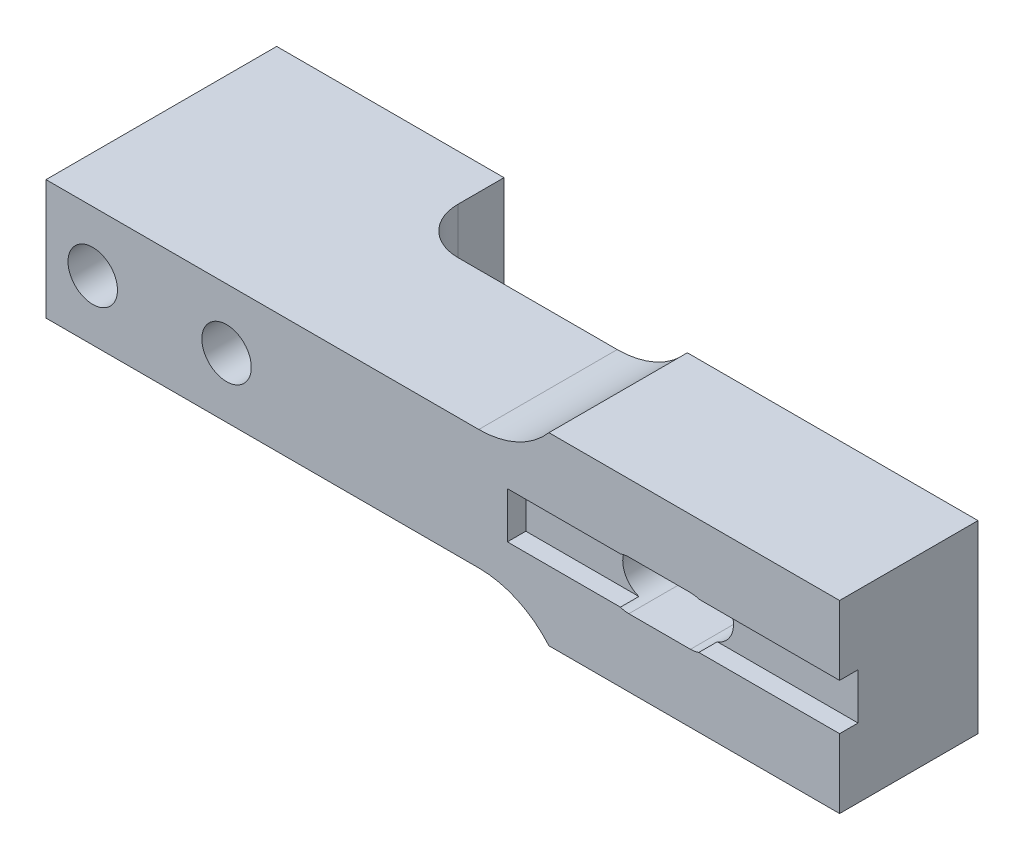
SolidWorks part; units mm, degrees
ref_plane "Front Plane" through (0, 0, 0) normal (0, 0, 1) x (1, 0, 0)
ref_plane "Top Plane" through (0, 0, 0) normal (0, 1, 0) x (1, 0, 0)
ref_plane "Right Plane" through (0, 0, 0) normal (1, 0, 0) x (0, 0, -1)
sketch "Sketch1" plane through (0, 0, 0) normal (0, 0, 1) x (1, 0, 0)
  line L0 (0, 0) -> (80, 0) construction
  line L1 (0, 13) -> (24.634, 13)
  line L2 (0, 13) -> (0, 0)
  line L3 (0, 0) -> (24.634, 0)
  line L4 (24.634, 13) -> (24.634, 0)
  line L5 (5.067, 6.5) -> (0, 6.5) construction
  line L6 (24.634, 6.5) -> (19.567, 6.5) construction
extrude "Boss-Extrude1" add sketch "Sketch1" along normal blind 10
sketch "Sketch4" plane through (0, 0, 10) normal (0, 0, 1) x (1, 0, 0)
  line L0 (24.634, 13) -> (0, 13) construction
  line L1 (0, 0) -> (82.5, 0)
  line L2 (0, 0) -> (0, 13)
  line L3 (0, 13) -> (82.5, 13)
  line L4 (82.5, 0) -> (82.5, 13)
  line L5 (80, 0) -> (80, 13) construction
  dimension "D1" = 2.5
extrude "Boss-Extrude4" add sketch "Sketch4" along normal blind 15
sketch "Sketch5" plane through (0, 0, 25) normal (0, 0, 1) x (1, 0, 0)
  line L0 (82.5, 0) -> (82.5, 13) construction
  line L1 (54.5, -3.5) -> (82.5, -3.5)
  line L2 (54.5, -3.5) -> (54.5, 0)
  line L3 (54.5, 16.5) -> (82.5, 16.5)
  line L4 (82.5, -3.5) -> (82.5, 0)
  line L5 (54.5, -3.5) -> (82.5, 16.5) construction
  line L6 (68.5, 0) -> (68.5, 13) construction
  line L7 (0, 0) -> (82.5, 0) construction
  line L8 (82.5, 13) -> (0, 13) construction
  line L9 (54.5, 0) -> (82.5, 0)
  line L10 (82.5, 13) -> (54.5, 13)
  line L11 (54.5, 13) -> (54.5, 16.5)
  line L12 (82.5, 13) -> (82.5, 16.5)
  point P13 (68.5, 6.5)
  point P14 (68.5, 6.5)
  dimension "D1" = 20
  dimension "D2" = 28
extrude "Boss-Extrude5" add sketch "Sketch5" against normal up to surface (15 mm away) up to face at (53.567, 6.5, 10)
sketch "Sketch6" plane through (0, 0, 25) normal (0, 0, 1) x (1, 0, 0)
  line L0 (54.5, 0) -> (54.5, 13) construction
  line L1 (63.16, 6.5) -> (69.84, 6.5) construction
  line L2 (63.16, 9.16) -> (69.84, 9.16)
  line L3 (63.16, 3.84) -> (69.84, 3.84)
  arc A0 (63.16, 9.16) -> (63.16, 3.84) centre (63.16, 6.5) ccw
  arc A1 (69.84, 3.84) -> (69.84, 9.16) centre (69.84, 6.5) ccw
  point P6 (66.5, 6.5)
  point P15 (54.5, 6.5)
  point P16 (60.5, 6.5)
  point P17 (72.5, 6.5)
  dimension "D1" = 5.32
  dimension "D2" = 6
  dimension "D3" = 12
extrude "Cut-Extrude1" cut sketch "Sketch6" against normal through all
sketch "Sketch7" plane through (0, 0, 25) normal (0, 0, 1) x (1, 0, 0)
  line L0 (50, 13) -> (50, 0) construction
  line L1 (50, 6.5) -> (82.5, 6.5) construction
  line L2 (82.5, -3.5) -> (82.5, 16.5) construction
  line L3 (66.25, 6.5) -> (66.25, 9) construction
  line L4 (50, 9) -> (82.5, 9)
  line L5 (50, 9) -> (50, 4)
  line L6 (50, 4) -> (82.5, 4)
  line L7 (82.5, 9) -> (82.5, 4)
  line L8 (66.25, 6.5) -> (66.25, 4) construction
  line L9 (0, 0) -> (54.5, 0) construction
  line L10 (54.5, 13) -> (0, 13) construction
  line L11 (54.5, 16.5) -> (54.5, 13) construction
  dimension "D1" = 5
  dimension "D2" = 4.5
extrude "Cut-Extrude2" cut sketch "Sketch7" against normal blind 2
sketch "Sketch11" plane through (0, 0, 0) normal (0, 0, -1) x (-1, 0, 0)
  line L0 (0, 6.5) -> (-24.634, 6.5) construction
  line L1 (0, 13) -> (0, 0) construction
  line L2 (-24.634, 0) -> (-24.634, 13) construction
  circle A0 centre (-5.067, 6.5) radius 2.68
  circle A1 centre (-19.567, 6.5) radius 2.68
  dimension "D3" = 5.36
  dimension "D4" = 5.36
  dimension "D1" = 5.067
  dimension "D2" = 14.5
extrude "Cut-Extrude3" cut sketch "Sketch11" against normal through all
fillet "Fillet1" radius 10 2 edges at (54.5, 13, 17.5) (54.5, 0, 17.5)
fillet "Fillet2" radius 5 1 edges at (24.634, 6.5, 10)
sketch "Sketch12" plane through (82.5, 0, 0) normal (1, 0, 0) x (0, 0, -1)
  line L8 (-25, 16.5) -> (-25, 9)
  line L9 (-25, 9) -> (-23, 9)
  line L10 (-23, 9) -> (-23, 4)
  line L11 (-23, 4) -> (-25, 4)
  line L12 (-25, 4) -> (-25, -3.5)
  line L13 (-25, -3.5) -> (-10, -3.5)
  line L14 (-10, -3.5) -> (-10, 16.5)
  line L15 (-10, 16.5) -> (-25, 16.5)
  line L16 (-25, 16.5) -> (-25, 9)
  line L17 (-25, 9) -> (-23, 9)
  line L18 (-23, 9) -> (-23, 4)
  line L19 (-23, 4) -> (-25, 4)
  line L20 (-25, 4) -> (-25, -3.5)
  line L21 (-25, -3.5) -> (-10, -3.5)
  line L22 (-10, -3.5) -> (-10, 16.5)
  line L23 (-10, 16.5) -> (-25, 16.5)
  dimension "D1" = 0
extrude "Boss-Extrude6" add sketch "Sketch12" along normal blind 3.5
